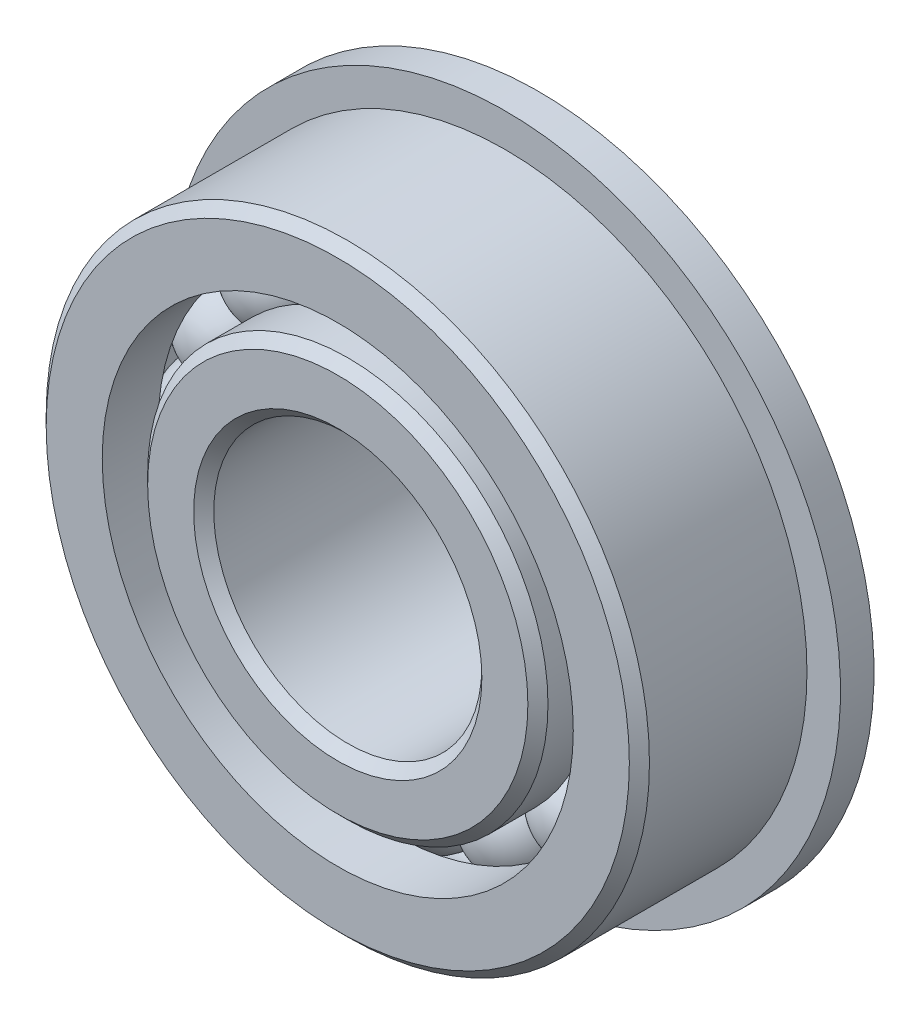
SolidWorks part; units mm, degrees
ref_plane "Front Plane" through (0, 0, 0) normal (0, 0, 1) x (1, 0, 0)
ref_plane "Top Plane" through (0, 0, 0) normal (0, 1, 0) x (1, 0, 0)
ref_plane "Right Plane" through (0, 0, 0) normal (1, 0, 0) x (0, 0, -1)
sketch "Sketch1" plane through (0, 0, 0) normal (1, 0, 0) x (0, 0, -1)
  line L0 (-4.7625, 0) -> (4.7625, 0) construction
  line L1 (0, 14.2875) -> (0, -14.2875) construction
  line L2 (4.2863, 14.2875) -> (-4.2863, 14.2875)
  line L3 (-4.2863, 14.2875) -> (-4.7625, 13.8113)
  line L4 (-4.7625, 13.8113) -> (-4.7625, 11.1561)
  line L5 (-4.7625, 11.1561) -> (-2.1167, 11.1561)
  line L6 (4.7625, 11.1561) -> (2.1167, 11.1561)
  line L7 (4.7625, 13.8113) -> (4.7625, 11.1561)
  line L8 (4.2863, 14.2875) -> (4.7625, 13.8113)
  line L9 (0, 14.2875) -> (0, 10.3187) construction
  line L10 (0, 10.3187) -> (0, 6.35) construction
  arc A0 (-2.1167, 11.1561) -> (2.1167, 11.1561) centre (0, 10.3187) cw
  point P14 (0, 6.35)
  dimension "Width" = 9.525
  dimension "OD" = 28.575
  dimension "D1" = 45
  dimension "D2" = 0.4763
  dimension "D3" = 4.2333
  dimension "D4" = 0.8374
revolve "Revolve1" add sketch "Sketch1" angle 360 about L0
sketch "Sketch3" plane through (0, 0, 0) normal (1, 0, 0) x (0, 0, -1)
  line L0 (-2.1167, 9.4814) -> (-4.7625, 9.4814) construction
  line L1 (-4.7625, 13.8113) -> (-4.7625, 11.1561) construction
  line L2 (-4.2863, 14.2875) -> (-4.7625, 13.8113) construction
  line L3 (-4.7625, 9.4814) -> (-4.7625, 6.8263) construction
  line L4 (-4.7625, 6.8263) -> (-4.7625, 9.0051)
  line L5 (-4.7625, 6.8263) -> (-4.2863, 6.35)
  line L6 (-4.2863, 6.35) -> (5.8737, 6.35)
  line L7 (-4.7625, 13.8113) -> (-4.7625, -13.8113) construction
  line L8 (5.8737, 6.35) -> (6.35, 6.8262)
  line L10 (6.35, 6.8262) -> (6.35, 9.4814) construction
  line L11 (6.35, 9.4814) -> (2.1167, 9.4814) construction
  line L12 (0, 14.2875) -> (0, -14.2875) construction
  line L13 (4.2863, 14.2875) -> (4.7625, 13.8113) construction
  line L14 (-4.7625, 9.0051) -> (-4.2863, 9.4814)
  line L15 (-4.2863, 9.4814) -> (-2.1167, 9.4814)
  line L16 (2.1167, 9.4814) -> (5.8737, 9.4814)
  line L17 (5.8737, 9.4814) -> (6.35, 9.0051)
  line L18 (6.35, 9.0051) -> (6.35, 6.8262)
  arc A1 (2.1167, 9.4814) -> (-2.1167, 9.4814) centre (0, 10.3187) cw
  arc A2 (2.1167, 11.1561) -> (-2.1167, 11.1561) centre (0, 10.3187) ccw construction
  dimension "D1" = 45
  dimension "Ring Wd" = 11.1125
revolve "Revolve3" add sketch "Sketch3" angle 360 about L0
sketch "Sketch4" plane through (0, 0, 0) normal (1, 0, 0) x (0, 0, -1)
  line L0 (-2.2763, 10.3187) -> (2.2763, 10.3187)
  arc A2 (-2.2763, 10.3187) -> (2.2763, 10.3187) centre (0, 10.3187) cw
  arc A3 (2.1167, 11.1561) -> (-2.1167, 11.1561) centre (0, 10.3187) ccw construction
revolve "Revolve4" add sketch "Sketch4" angle 360 about L0
ref_axis "Axis1" through (0, 0, -4.7625) along (0, 0, 1)
pattern_circular "CirPattern1" count 16 every 22.5 about axis through (0, 0, -4.7625) along (0, 0, 1) of bodies 104
sketch "Sketch5" plane through (0, 0, 0) normal (1, 0, 0) x (0, 0, -1)
  line L0 (-4.7625, 11.1561) -> (-2.1167, 11.1561) construction
  line L1 (-4.5244, 11.1561) -> (-2.2763, 11.1561)
  line L2 (-4.5244, 11.1561) -> (-4.5244, 9.4814)
  line L3 (-4.5244, 9.4814) -> (-2.2763, 9.4814)
  line L4 (-2.2763, 11.1561) -> (-2.2763, 9.4814)
  line L5 (-2.1167, 9.4814) -> (-4.7625, 9.4814) construction
  line L6 (4.7625, 11.1561) -> (2.1167, 11.1561) construction
  line L7 (4.5244, 11.1561) -> (2.2763, 11.1561)
  line L8 (4.5244, 11.1561) -> (4.5244, 9.4814)
  line L9 (4.5244, 9.4814) -> (2.2763, 9.4814)
  line L10 (2.2763, 11.1561) -> (2.2763, 9.4814)
  line L11 (6.35, 9.4814) -> (2.1167, 9.4814) construction
  line L12 (-4.2863, 14.2875) -> (-4.7625, 13.8113) construction
  point P18 (-4.5244, 14.0494)
revolve "Revolve5" [suppressed] add sketch "Sketch5" angle 360 about L0
sketch "Sketch6" plane through (0, 0, 0) normal (1, 0, 0) x (0, 0, -1)
  line L1 (4.7625, 11.1561) -> (3.175, 11.1561)
  line L2 (4.7625, 11.1561) -> (4.7625, 15.875)
  line L3 (4.7625, 15.875) -> (3.175, 15.875)
  line L4 (3.175, 11.1561) -> (3.175, 15.875)
  line L5 (4.7625, 0) -> (-4.7625, 0) construction
  dimension "Flange OD" = 31.75
  dimension "Th" = 1.5875
revolve "Revolve6" add sketch "Sketch6" angle 360 about L5
equation "\"D2@Sketch1\" = \"Width@Sketch1\"*.05"
equation "\"D3@Sketch1\" = \"Width@Sketch1\"/2.25"
equation "\"D4@Sketch1\" = (((\"OD@Sketch1\"-\"Width@Sketch1\")/2)/3.25)/3.5"
equation "\"D2@CirPattern1\" = 360/\"Balls@CirPattern1\""
